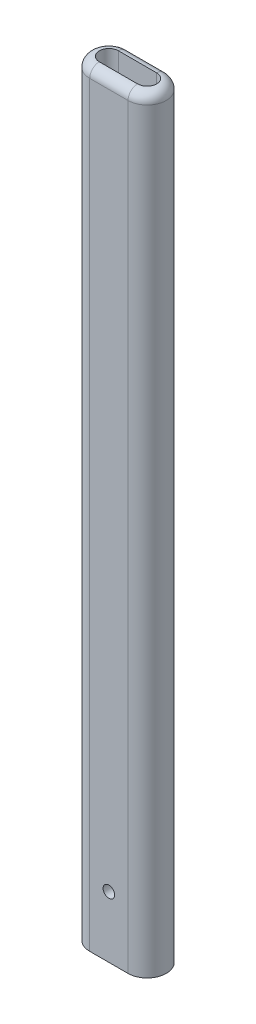
SolidWorks part; units mm, degrees
ref_plane "Front Plane" through (0, 0, 0) normal (0, 0, 1) x (1, 0, 0)
ref_plane "Top Plane" through (0, 0, 0) normal (0, 1, 0) x (1, 0, 0)
ref_plane "Right Plane" through (0, 0, 0) normal (1, 0, 0) x (0, 0, -1)
sketch "Sketch1" plane through (0, 0, 0) normal (0, 1, 0) x (1, 0, 0)
  line L0 (-15, 5) -> (5, 5)
  line L1 (-15, 10) -> (5, 10)
  line L2 (-15, -10) -> (5, -10)
  line L3 (-15, -5) -> (5, -5)
  arc A0 (5, -10) -> (5, 10) centre (5, 0) ccw
  arc A1 (-15, 10) -> (-15, -10) centre (-15, 0) ccw
  arc A2 (5, -5) -> (5, 5) centre (5, 0) ccw
  arc A3 (-15, 5) -> (-15, -5) centre (-15, 0) ccw
  point P4 (0, 0)
  dimension "D1" = 5
  dimension "D2" = 10
  dimension "D3" = 5
  dimension "D4" = 20
extrude "Boss-Extrude1" add sketch "Sketch1" along normal mid plane 400
sketch "Sketch2" plane through (0, 0, 10) normal (0, 0, 1) x (1, 0, 0)
  circle A0 centre (-5, -168) radius 3
extrude "Cut-Extrude1" cut sketch "Sketch2" against normal through all
fillet "Fillet1" radius 5 4 edges at (-25, 200, 0) (-5, 200, -10) (15, 200, 0) (-5, 200, 10)
